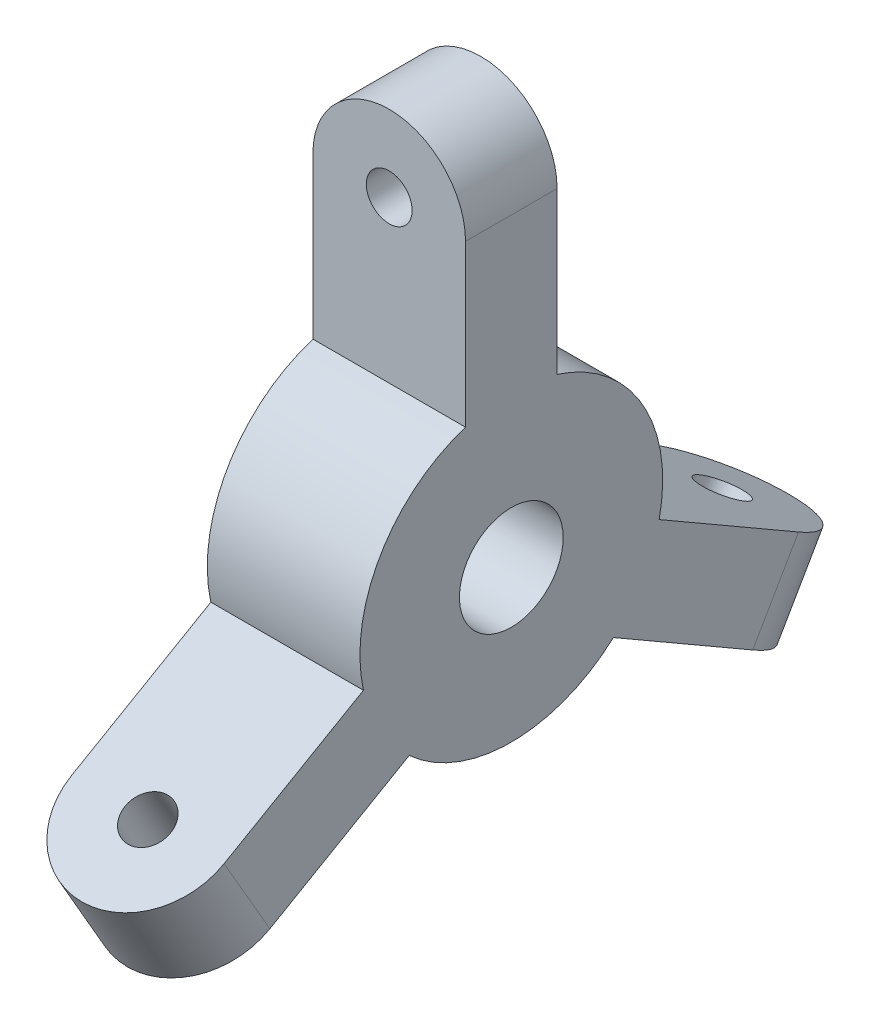
SolidWorks part; units mm, degrees
ref_plane "Plan de face" through (0, 0, 0) normal (0, 0, 1) x (1, 0, 0)
ref_plane "Plan de dessus" through (0, 0, 0) normal (0, 1, 0) x (1, 0, 0)
ref_plane "Plan de droite" through (0, 0, 0) normal (1, 0, 0) x (0, 0, -1)
sketch "Esquisse1" plane through (0, 0, 0) normal (1, 0, 0) x (0, 0, -1)
  line L0 (0, 0) -> (0, 25) construction
  line L1 (-3, 25) -> (3, 25)
  line L2 (-3, 25) -> (-3, 9.4555)
  line L3 (3, 25) -> (3, 9.4555)
  line L4 (23.1506, -9.9019) -> (9.6887, -2.1297)
  line L5 (23.1506, -9.9019) -> (20.1506, -15.0981)
  line L6 (20.1506, -15.0981) -> (6.6887, -7.3258)
  line L7 (-20.1506, -15.0981) -> (-6.6887, -7.3258)
  line L8 (-20.1506, -15.0981) -> (-23.1506, -9.9019)
  line L9 (-23.1506, -9.9019) -> (-9.6887, -2.1297)
  arc A0 (3, 9.4555) -> (9.6887, -2.1297) centre (0, 0) cw
  arc A1 (6.6887, -7.3258) -> (-6.6887, -7.3258) centre (0, 0) cw
  arc A2 (-9.6887, -2.1297) -> (-3, 9.4555) centre (0, 0) cw
  circle A3 centre (0, 0) radius 9.92 construction
  point P21 (0, 0)
  dimension "D4" = 9.92
  dimension "D1" = 25
  dimension "D2" = 6
  dimension "D3" = 3
extrude "Boss.-Extru.1" add sketch "Esquisse1" along normal blind 5 and the other way blind 5
hole_wizard "Trou taraudé M81" positions "Esquisse3" profile "Esquisse4" tap size "M8" standard "ISO" end condition through all
sketch "Esquisse3" plane through (5, 0, 0) normal (1, 0, 0) x (0, 0, -1)
  point P0 (0, 0)
sketch "Esquisse4" plane through (5, 0, 0) normal (0, 1, 0) x (0, 0, -1)
  line L0 (0, 0) -> (0, 10)
  line L1 (0, 10) -> (3.4, 10)
  line L2 (3.4, 10) -> (3.4, 0)
  line L5 (3.4, 0) -> (0, 0)
  line L11 (0, -6.35) -> (0, 107.95) construction
  dimension "Diamètre du trou pour taraudage jusqu'au prochain" = 6.8
  dimension "Profondeur du trou pour taraudage jusqu'au prochain" = 10
cosmetic thread "Filetage de perçage1" parameters "D2"=8
sketch "Esquisse5" plane through (0, 0, 3) normal (0, 0, 1) x (1, 0, 0)
  line L0 (0, 25) -> (0, 0) construction
  line L2 (-5, 9.4555) -> (-5, 20)
  line L3 (-5, 25) -> (-5, 9.4555) construction
  line L4 (-5, 9.4555) -> (-13.1992, 9.4555)
  line L5 (-13.1992, 9.4555) -> (-13.1992, 30)
  line L6 (-13.1992, 30) -> (13.6203, 30)
  line L7 (13.6203, 30) -> (13.6203, 9.4555)
  line L8 (13.6203, 9.4555) -> (5, 9.4555)
  line L9 (5, 9.4555) -> (5, 20)
  line L10 (5, 25) -> (5, 9.4555) construction
  line L11 (-5, 25) -> (5, 25) construction
  arc A1 (-5, 20) -> (5, 20) centre (0, 20) cw
  circle A2 centre (0, 20) radius 1.5
  point P1 (0, 19.3495)
  dimension "D1" = 3
  dimension "D2" = 8.1992
  dimension "D3" = 8.6203
  dimension "D4" = 5
  dimension "D5" = 20
extrude "Enlèv. mat.-Extru.1" cut sketch "Esquisse5" against normal through all
pattern_circular "Répétition circulaire1" count 3 over 360 about axis through (5, 0, 0) along (1, 0, 0) of "Enlèv. mat.-Extru.1"
